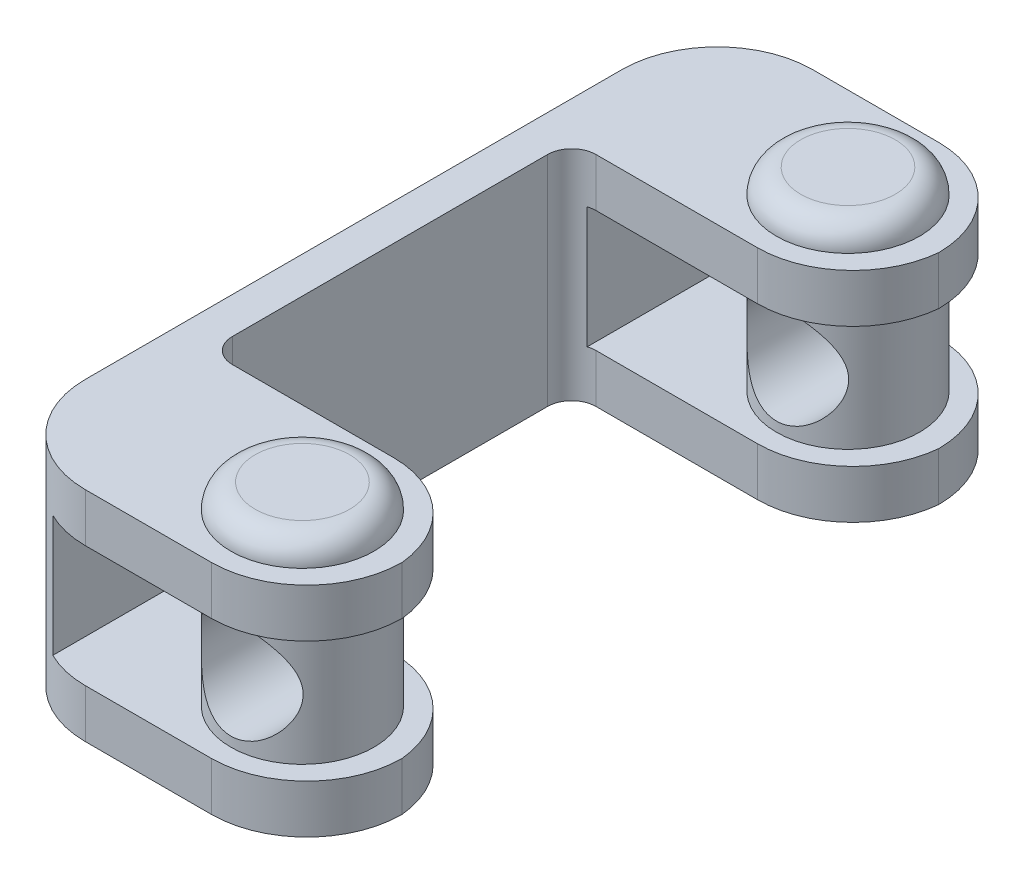
SolidWorks part; units mm, degrees
ref_plane "Front Plane" through (0, 0, 0) normal (0, 0, 1) x (1, 0, 0)
ref_plane "Top Plane" through (0, 0, 0) normal (0, 1, 0) x (1, 0, 0)
ref_plane "Right Plane" through (0, 0, 0) normal (1, 0, 0) x (0, 0, -1)
sketch "Sketch7" plane through (0, 0, 0) normal (0, 0, 1) x (1, 0, 0)
  line L1 (-30.2217, -17.2167) -> (2.9755, -17.2167)
  line L2 (-30.2217, -17.2167) -> (-30.2217, -22.2967)
  line L3 (-24.6692, -22.2967) -> (2.9755, -22.2967)
  line L4 (2.9755, -17.2167) -> (2.9755, -22.2967)
  line L6 (-30.2217, -22.2967) -> (-30.2217, -34.9967)
  line L8 (-24.6692, -22.2967) -> (-24.6692, -34.9967)
  line L9 (-24.6692, -34.9967) -> (2.9755, -34.9967)
  line L10 (-30.2217, -34.9967) -> (-30.2217, -40.0767)
  line L11 (-30.2217, -40.0767) -> (2.9755, -40.0767)
  line L12 (2.9755, -34.9967) -> (2.9755, -40.0767)
  dimension "D1" = 5.08
  dimension "D2" = 5.08
  dimension "D3" = 12.7
extrude "Boss-Extrude4" add sketch "Sketch7" along normal blind 76.2 contours L1 L4 L3 L8 L9 L12 L11 L10 L6 L2
fillet "Fillet1" radius 10 6 edges at (-30.2217, -28.6467, 76.2) (2.9755, -37.5367, 76.2) (2.9755, -19.7567, 76.2) (-30.2217, -28.6467, 0) (2.9755, -37.5367, 0) (2.9755, -19.7567, 0)
sketch "Sketch8" plane through (0, -17.2167, 0) normal (0, 1, 0) x (1, 0, 0)
  line L0 (-13.6231, -76.2) -> (-13.6231, -57.15) construction
  line L1 (-20.2217, -76.2) -> (-7.0245, -76.2) construction
  line L2 (-13.6231, 0) -> (-13.6231, -19.05) construction
  line L3 (-20.2217, 0) -> (-7.0245, 0) construction
  line L4 (2.9755, -66.2) -> (2.9755, -10) construction
  line L5 (2.9755, -57.15) -> (-26.4117, -57.15)
  line L6 (2.9755, -57.15) -> (2.9755, -19.05)
  line L7 (2.9755, -19.05) -> (-26.4117, -19.05)
  line L8 (-26.4117, -57.15) -> (-26.4117, -19.05)
  line L9 (-30.2217, -38.1) -> (-26.4117, -38.1) construction
  line L10 (-30.2217, -66.2) -> (-30.2217, -10) construction
  dimension "D1" = 19.05
  dimension "D2" = 19.05
  dimension "D3" = 3.81
extrude "Cut-Extrude2" cut sketch "Sketch8" against normal blind 25.4
fillet "Fillet2" radius 10 4 edges at (2.9755, -37.5367, 57.15) (2.9755, -37.5367, 19.05) (2.9755, -19.7567, 19.05) (2.9755, -19.7567, 57.15)
sketch "Sketch9" plane through (0, -17.2167, 0) normal (0, 1, 0) x (1, 0, 0)
  line L0 (-7.0245, -76.2) -> (-6.9793, -57.15) construction
  line L1 (-6.9793, -19.05) -> (-7.0245, 0) construction
  circle A0 centre (-7.0019, -66.675) radius 7.493
  circle A1 centre (-7.0019, -9.525) radius 7.493
  dimension "D1" = 14.986
  dimension "D2" = 14.986
extrude "Boss-Extrude5" add sketch "Sketch9" along normal blind 2.54
fillet "Fillet4" radius 2.54 2 edges at (-7.0019, -14.6767, 17.018) (-7.0019, -14.6767, 74.168)
sketch "Sketch10" plane through (0, -34.9967, 0) normal (0, 1, 0) x (1, 0, 0)
  line L0 (-7.0245, -76.2) -> (-6.9793, -57.15) construction
  line L1 (-6.9793, -19.05) -> (-7.0245, 0) construction
  circle A0 centre (-7.0019, -66.675) radius 7.493
  circle A1 centre (-7.0019, -9.525) radius 7.493
  dimension "D1" = 14.986
  dimension "D2" = 14.986
extrude "Boss-Extrude6" add sketch "Sketch10" along normal up to next
sketch "Sketch11" plane through (0, 0, 76.2) normal (0, 0, 1) x (1, 0, 0)
  line L0 (-14.4949, -28.6467) -> (0.4911, -28.6467) construction
  line L1 (-14.4949, -22.2967) -> (-14.4949, -34.9967) construction
  line L2 (0.4911, -34.9967) -> (0.4911, -22.2967) construction
  line L3 (-7.0019, -22.2967) -> (-7.0245, -34.9967) construction
  line L4 (-14.4949, -22.2967) -> (0.4911, -22.2967) construction
  circle A0 centre (-7.0019, -28.6467) radius 5.334
  dimension "D1" = 10.668
extrude "Cut-Extrude3" cut sketch "Sketch11" against normal blind 76.2
fillet "Fillet5" radius 2.54 2 edges at (-26.4117, -28.6467, 57.15) (-26.4117, -28.6467, 19.05)
sketch "Sketch12" plane through (-30.2217, 0, 0) normal (-1, 0, 0) x (0, 0, 1)
  line L0 (10, -28.6467) -> (66.2, -28.6467) construction
  line L1 (10, -17.2167) -> (10, -40.0767) construction
  line L2 (66.2, -40.0767) -> (66.2, -17.2167) construction
  line L3 (38.1, -17.2167) -> (38.1, -36.2667) construction
  line L4 (66.2, -17.2167) -> (10, -17.2167) construction
  line L5 (66.2, -40.0767) -> (10, -40.0767) construction
  line L7 (29.21, -40.0767) -> (38.1, -40.0767)
  line L8 (29.21, -40.0767) -> (29.21, -36.2667)
  line L9 (29.21, -36.2667) -> (38.1, -36.2667)
  line L11 (38.1, -36.2667) -> (46.99, -36.2667)
  line L13 (38.1, -40.0767) -> (46.99, -40.0767)
  line L14 (46.99, -36.2667) -> (46.99, -40.0767)
  dimension "D1" = 8.89
  dimension "D2" = 3.81
  dimension "D3" = 8.89
extrude "Boss-Extrude7" add sketch "Sketch12" along normal blind 12.7
fillet "Fillet6" radius 2.54 2 edges at (-42.9217, -38.1717, 46.99) (-42.9217, -38.1717, 29.21)
sketch "Sketch13" plane through (0, -36.2667, 0) normal (0, 1, 0) x (1, 0, 0)
  line L0 (-35.3017, -46.99) -> (-35.3017, -29.21) construction
  line L1 (-40.3817, -46.99) -> (-30.2217, -46.99) construction
  line L2 (-40.3817, -29.21) -> (-30.2217, -29.21) construction
  line L3 (-30.2217, -38.1) -> (-42.9217, -38.1) construction
  line L4 (-30.2217, -46.99) -> (-30.2217, -29.21) construction
  line L5 (-42.9217, -44.45) -> (-42.9217, -31.75) construction
  circle A0 centre (-36.5717, -38.1) radius 4.826
  dimension "D1" = 9.652
extrude "Cut-Extrude4" cut sketch "Sketch13" against normal blind 5.08
